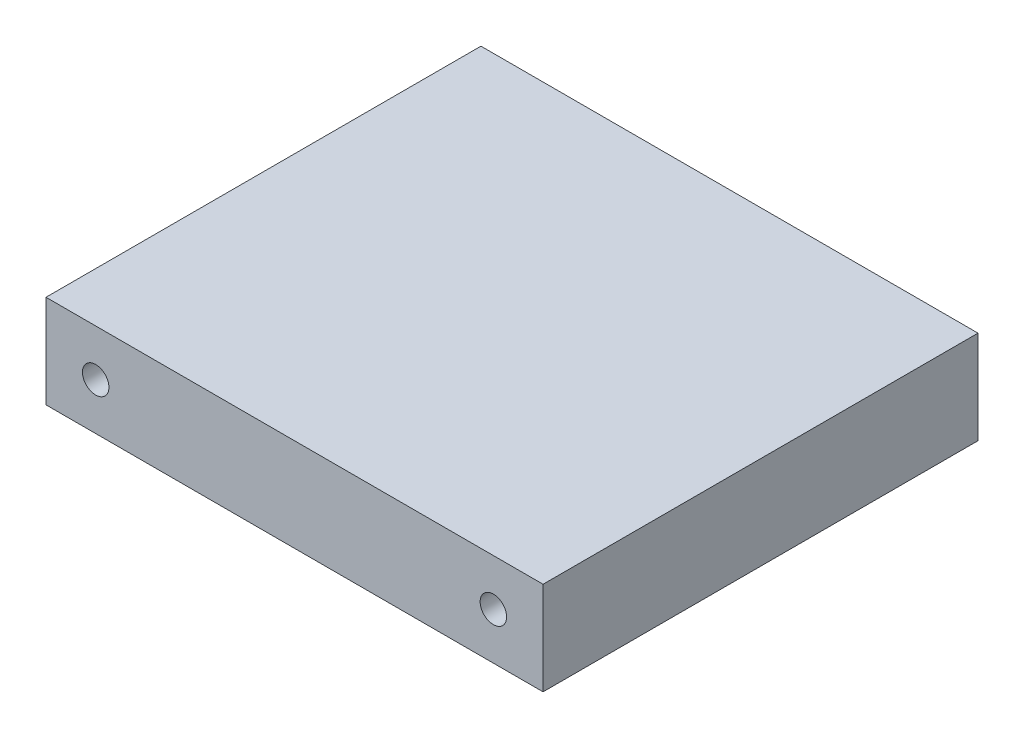
SolidWorks part; units mm, degrees
ref_plane "Front Plane" through (0, 0, 0) normal (0, 0, 1) x (1, 0, 0)
ref_plane "Top Plane" through (0, 0, 0) normal (0, 1, 0) x (1, 0, 0)
ref_plane "Right Plane" through (0, 0, 0) normal (1, 0, 0) x (0, 0, -1)
sketch "Sketch2" plane through (0, 0, 0) normal (0, 1, 0) x (1, 0, 0)
  line L1 (-25.4, 22.225) -> (25.4, 22.225)
  line L2 (-25.4, 22.225) -> (-25.4, -22.225)
  line L3 (-25.4, -22.225) -> (25.4, -22.225)
  line L4 (25.4, 22.225) -> (25.4, -22.225)
  line L5 (-25.4, 22.225) -> (25.4, -22.225) construction
  line L6 (-25.4, -22.225) -> (25.4, 22.225) construction
  point P0 (0, 0)
  dimension "D1" = 50.8
  dimension "D2" = 44.45
extrude "Boss-Extrude1" add sketch "Sketch2" along normal blind 9.525 contours L2 L3 L4 L1
sketch "Sketch3" plane through (0, 0, 22.225) normal (0, 0, 1) x (1, 0, 0)
  line L0 (25.4, 9.525) -> (25.4, 0) construction
  line L1 (-25.4, 9.525) -> (-25.4, 0) construction
  circle A0 centre (20.32, 4.7625) radius 1.8415
  circle A1 centre (-20.32, 4.7625) radius 1.8415
  point P4 (0, 0)
  point P7 (25.4, 4.7625)
  point P8 (0, 0)
  dimension "D1" = 5.08
  dimension "D2" = 5.08
hole_wizard "#6-32 Tapped Hole1" positions "Sketch4" profile "Sketch5" tap size "#6-32" standard "ANSI Inch"
sketch "Sketch4" plane through (0, 0, 22.225) normal (0, 0, 1) x (1, 0, 0)
  circle A0 centre (-20.32, 4.7625) radius 1.8415 construction
  circle A1 centre (20.32, 4.7625) radius 1.8415 construction
  point P0 (-20.32, 4.7625)
  point P2 (20.32, 4.7625)
  point P18 (-20.32, 4.7625)
  point P22 (20.32, 4.7625)
sketch "Sketch5" plane through (-20.32, 4.7625, 22.225) normal (1, 0, 0) x (0, -1, 0)
  line L0 (0, 0) -> (0, 10.2107)
  line L1 (0, 10.2107) -> (1.3525, 9.398)
  line L2 (1.3525, 9.398) -> (1.3525, 0)
  line L5 (1.3525, 0) -> (0, 0)
  line L10 (0, 10.2107) -> (-1.3526, 9.398) construction
  line L11 (0, -6.35) -> (0, 107.95) construction
  dimension "Tap Drill Dia." = 2.7051
  dimension "Tap Drill Depth" = 9.398
  dimension "Drill Angle" = 118
cosmetic thread "Hole Thread1" parameters "D1"=7.112, "D2"=3.5052
cosmetic thread "Hole Thread2" parameters "D1"=7.112, "D2"=3.5052
hole_wizard "#6-32 Tapped Hole2" positions "Sketch6" profile "Sketch7" tap size "#6-32" standard "ANSI Inch"
sketch "Sketch6" plane through (0, 0, -22.225) normal (0, 0, -1) x (-1, 0, 0)
  circle A0 centre (-20.32, 4.7625) radius 1.8415 construction
  circle A1 centre (20.32, 4.7625) radius 1.8415 construction
  point P0 (-20.32, 4.7625)
  point P2 (20.32, 4.7625)
  point P4 (-20.32, 4.7625)
  point P8 (20.32, 4.7625)
sketch "Sketch7" plane through (20.32, 4.7625, -22.225) normal (1, 0, 0) x (0, 1, 0)
  line L0 (0, 0) -> (0, 10.2107)
  line L1 (0, 10.2107) -> (1.3525, 9.398)
  line L2 (1.3525, 9.398) -> (1.3525, 0)
  line L5 (1.3525, 0) -> (0, 0)
  line L10 (0, 10.2107) -> (-1.3525, 9.398) construction
  line L11 (0, -6.35) -> (0, 107.95) construction
  dimension "Tap Drill Dia." = 2.7051
  dimension "Tap Drill Depth" = 9.398
  dimension "Drill Angle" = 118
cosmetic thread "Hole Thread3" parameters "D1"=7.112, "D2"=3.5052
cosmetic thread "Hole Thread4" parameters "D1"=7.112, "D2"=3.5052
